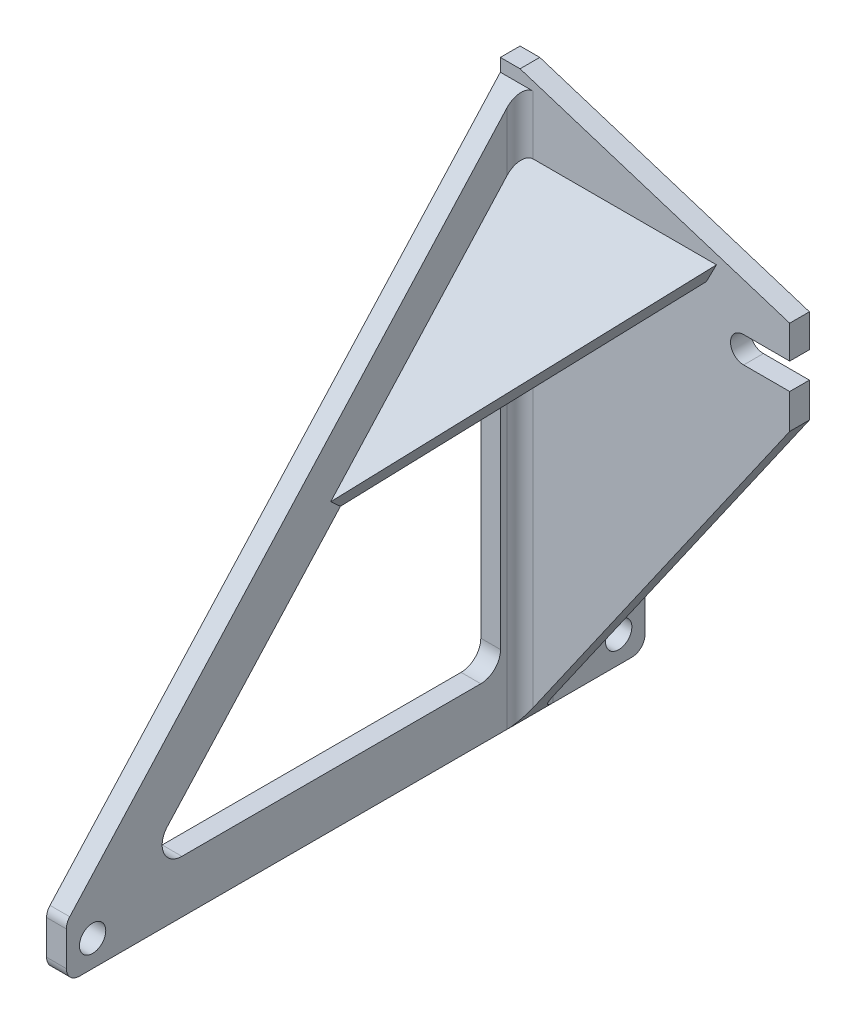
SolidWorks part; units mm, degrees
ref_plane "Спереди" through (0, 0, 0) normal (0, 0, 1) x (1, 0, 0)
ref_plane "Сверху" through (0, 0, 0) normal (0, 1, 0) x (1, 0, 0)
ref_plane "Справа" through (0, 0, 0) normal (1, 0, 0) x (0, 0, -1)
sketch "AXTSide" plane through (0, 0, 0) normal (1, 0, 0) x (0, 0, -1)
  line L0 (25, 97.8915) -> (25, -28.4227) construction
  line L1 (-75, 86) -> (75, 86)
  line L2 (-75, 86) -> (-75, 0)
  line L3 (-75, 0) -> (75, 0)
  line L4 (75, 86) -> (75, 0)
  dimension "D1" = 150
  dimension "D2" = 86
  dimension "D3" = 50
sketch "Эскиз1" plane through (0, 0, 0) normal (1, 0, 0) x (0, 0, -1)
  line L0 (-44, 0) -> (44, 0)
  line L7 (-44, 8) -> (-44, 0)
  line L8 (0, -10.3997) -> (0, 20.0001) construction
  line L9 (44, 8) -> (44, 0)
  line L10 (-44, 8) -> (25, 84.049)
  line L11 (25, 97.8915) -> (25, -28.4227) construction
  line L12 (25, 84.049) -> (44, 8)
  line L13 (-28.647, 13.0159) -> (16.8064, 63.1127)
  line L14 (22.0282, 61.0969) -> (22.0282, 11)
  line L15 (19.0282, 8) -> (-26.4252, 8)
  circle A0 centre (-40, 4) radius 2
  circle A1 centre (40, 4) radius 2
  arc A7 (-28.647, 13.0159) -> (-26.4252, 8) centre (-26.4252, 11) ccw
  arc A8 (19.0282, 8) -> (22.0282, 11) centre (19.0282, 11) ccw
  arc A9 (22.0282, 61.0969) -> (16.8064, 63.1127) centre (19.0282, 61.0969) ccw
  point P4 (0, 0)
  point P13 (0, 0)
  point P18 (0, 8)
  point P20 (0, 0)
  point P23 (-34.1844, 8)
  point P25 (0, 0)
  point P26 (25.6031, 8)
  point P27 (22.7395, 5.0997)
  point P28 (0, 0)
  point P29 (22.0282, 74.6625)
  point P30 (24.1054, 71.1573)
  point P31 (-35.8721, 6.6361)
  point P32 (0, 0)
  point P33 (-37.3431, 8)
  dimension "D2" = 4
  dimension "D8" = 3
  dimension "D1" = 88
  dimension "D3" = 80
  dimension "D4" = 8
  dimension "D5" = 4
  dimension "D6" = 8
  dimension "D7" = 8
extrude "Бобышка-Вытянуть1" add sketch "Эскиз1" along normal blind 3
sketch "Эскиз2" plane through (0, 0, 0) normal (1, 0, 0) x (0, 0, -1)
  line L0 (-44, 0) -> (44, 0) construction
  line L1 (28, 0) -> (25, 0)
  line L2 (28, 0) -> (28, 86)
  line L3 (28, 86) -> (25, 86)
  line L4 (25, 0) -> (25, 86)
  line L6 (-75, -3.1242) -> (-75, 24.0657) construction
  line L7 (75, 86) -> (75, 0) construction
  line L8 (-75, 86) -> (75, 86) construction
  dimension "D1" = 50
  dimension "D2" = 35
  dimension "D3" = 3
extrude "Бобышка-Вытянуть2" add sketch "Эскиз2" along normal blind 44
sketch "Эскиз3" plane through (0, 0, -25) normal (0, 0, 1) x (1, 0, 0)
  line L0 (3, 86) -> (44, 73)
  line L1 (44, 86) -> (0, 86) construction
  line L2 (44, 86) -> (44, 0) construction
  line L3 (44, 73) -> (44, 68)
  line L4 (44, 68) -> (37, 68)
  line L5 (37, 64) -> (44, 64)
  line L6 (44, 64) -> (47.67, 64)
  line L14 (0, 86) -> (0, 84.049) construction
  line L15 (3, 0) -> (47.67, 64)
  line L16 (3, 0) -> (48.685, 0)
  line L17 (48.685, 0) -> (53.4141, 0)
  line L18 (53.4141, 0) -> (53.4141, 86)
  line L19 (53.4141, 86) -> (3, 86)
  arc A0 (37, 68) -> (37, 64) centre (37, 66) ccw
  point P10 (15.4767, 0)
  point P17 (3, 0)
  dimension "D5" = 5
  dimension "D1" = 20
  dimension "D6" = 4
  dimension "D7" = 3
extrude "Вырез-Вытянуть1" cut sketch "Эскиз3" against normal blind 3
fillet "Скругление1" radius 2 2 edges at (3, 36.0206, -28) (3, 42.0245, -25)
ref_axis "Ось1" through (50.5284, 72.1433, -25) along (-1, 0, 0)
sketch "Эскиз8" plane through (0, 20.1329, 22.1896) normal (0, -0.672, -0.7406) x (-1, 0, 0)
  line L0 (-3, 29.5792) -> (-32.4143, 71.7779)
  line L1 (-3, 58.0341) -> (-3, -9.6098) construction
  point P4 (-39.1699, 51.6029)
  point P5 (-29.956, 68.2653)
  point P6 (-32.4143, 71.7779)
  point P7 (0, 0)
  point P8 (-28.646, 66.4859)
rib "Ребро2" sketch "Эскиз8" sketch "Эскиз8" thickness 2 extrusion direction parallel to sketch draft on no parameters "D1"=2
fillet "Скругление2" radius 2 4 edges at (1.5, 8, -44) (1.5, 0, -44) (1.5, 8, 44) (1.5, 0, 44)
equation "\"D1@Бобышка-Вытянуть2\"=197-140-13"
